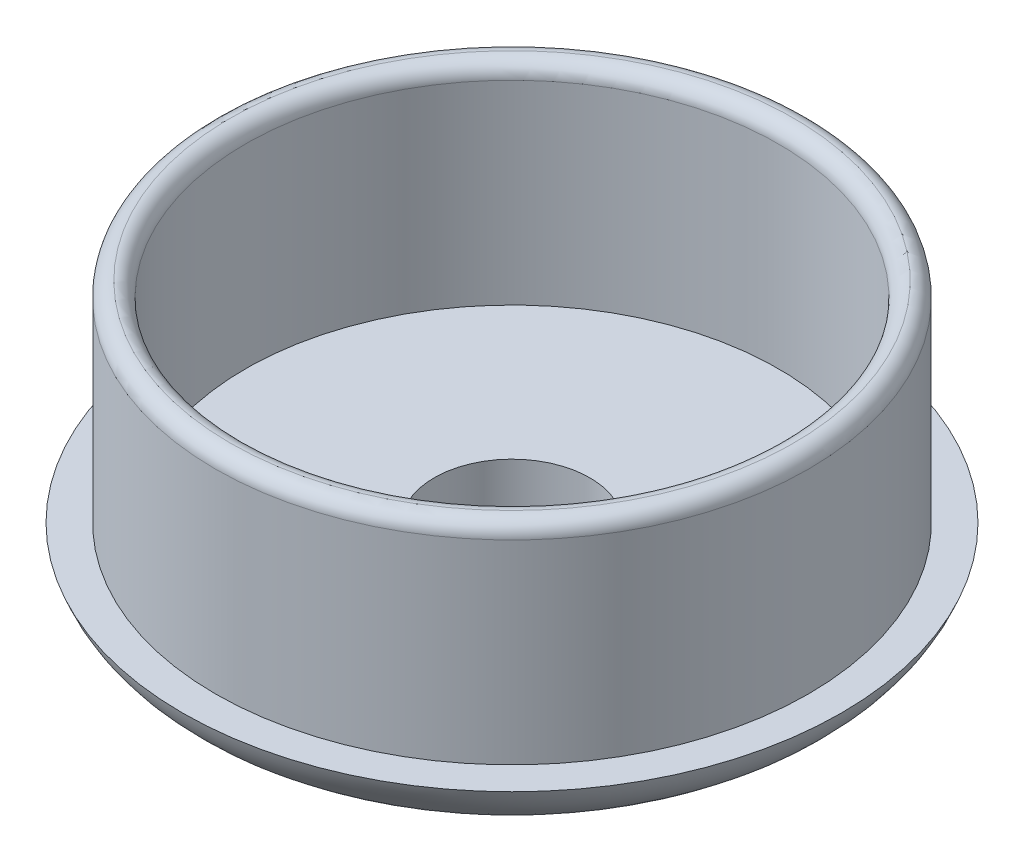
SolidWorks part; units mm, degrees
ref_plane "Front Plane" through (0, 0, 0) normal (0, 0, 1) x (1, 0, 0)
ref_plane "Top Plane" through (0, 0, 0) normal (0, 1, 0) x (1, 0, 0)
ref_plane "Right Plane" through (0, 0, 0) normal (1, 0, 0) x (0, 0, -1)
sketch "Sketch1" plane through (0, 0, 0) normal (0, 1, 0) x (1, 0, 0)
  circle A0 centre (0, 0) radius 11
  dimension "D1" = 22
extrude "Boss-Extrude1" add sketch "Sketch1" along normal blind 2
sketch "Sketch2" plane through (0, 2, 0) normal (0, 1, 0) x (1, 0, 0)
  circle A0 centre (0, 0) radius 9.9
  circle A1 centre (0, 0) radius 8.9
  dimension "D1" = 19.8
  dimension "D2" = 17.8
extrude "Boss-Extrude2" add sketch "Sketch2" along normal blind 7
sketch "Sketch3" plane through (0, 2, 0) normal (0, 1, 0) x (1, 0, 0)
  circle A0 centre (0, 0) radius 2.6
  dimension "D1" = 5.2
extrude "Cut-Extrude1" cut sketch "Sketch3" against normal through all
fillet "Fillet1" radius 3 1 edges at (0, 0, 11)
fillet "Fillet2" radius 0.5 2 edges at (0, 9, 8.9) (0, 9, 9.9)
